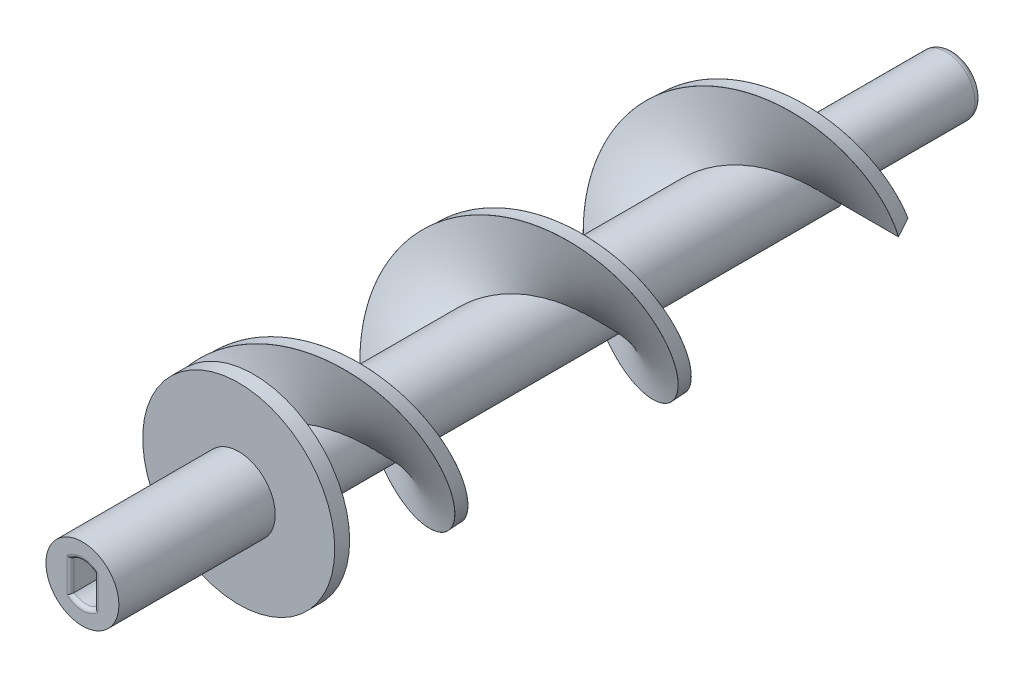
SolidWorks part; units mm, degrees
ref_plane "Front Plane" through (0, 0, 0) normal (0, 0, 1) x (1, 0, 0)
ref_plane "Top Plane" through (0, 0, 0) normal (0, 1, 0) x (1, 0, 0)
ref_plane "Right Plane" through (0, 0, 0) normal (1, 0, 0) x (0, 0, -1)
sketch "Sketch2" plane through (0, 0, 0) normal (0, 0, 1) x (1, 0, 0)
  circle A0 centre (0, 0) radius 4.9
  dimension "D1" = 9.8
extrude "Boss-Extrude1" add sketch "Sketch2" along normal mid plane 98
sketch "Sketch3" plane through (0, 0, -49) normal (0, 0, -1) x (-1, 0, 0)
  circle A0 centre (0, 0) radius 4
curve "Helix/Spiral1" pitch 30 height 75 radius 4 centre (0, 0, -49) axis (0, 0, 1) start towards (1, 0, 0)
ref_plane "Plane1" through (4, 0, -49) normal (0, 0.6422, 0.7666) x (1, 0, 0)
sketch "Sketch5" plane through (4, 0, -49) normal (0, 0.6422, 0.7666) x (1, 0, 0)
  line L1 (-0.1, 0) -> (8.89, 0)
  line L2 (-0.1, 0) -> (-0.1, -2)
  line L3 (-0.1, -2) -> (8.89, -2)
  line L4 (8.9, -0.01) -> (8.9, -1.99)
  arc A0 (8.89, -2) -> (8.9, -1.99) centre (8.89, -1.99) ccw
  arc A1 (8.89, 0) -> (8.9, -0.01) centre (8.89, -0.01) cw
  point P14 (8.9, 0)
  point P15 (0, 0)
  dimension "D3" = 0.01
  dimension "D4" = 1
  dimension "D1" = 9
  dimension "D2" = 2
sweep "Sweep1" add profiles "Sketch5" path "Helix/Spiral1"
sketch "Sketch6" plane through (0, 0, 49) normal (0, 0, 1) x (1, 0, 0)
  line L1 (-1.6, -2.0494) -> (1.6, -2.0494)
  line L2 (-1.6, -2.0494) -> (-1.6, 2.0494)
  line L3 (-1.6, 2.0494) -> (1.6, 2.0494)
  line L4 (1.6, -2.0494) -> (1.6, 2.0494)
  line L5 (-1.6, -2.0494) -> (1.6, 2.0494) construction
  line L6 (-1.6, 2.0494) -> (1.6, -2.0494) construction
  circle A0 centre (0, 0) radius 2.6
  dimension "D1" = 5.2
  dimension "D2" = 3.2
extrude "Cut-Extrude1" cut sketch "Sketch6" against normal blind 9 contours L3 A0 | L1 L4 L3 L2 | L1 A0 region at (0, 0, 49) region at (0, -2.2718, 49) region at (0, 2.2718, 49)
sketch "Sketch7" plane through (0, 0, -49) normal (0, 0, -1) x (-1, 0, 0)
  circle A0 centre (0, 0) radius 3.9
  dimension "D1" = 7.8
extrude "Boss-Extrude3" add sketch "Sketch7" along normal blind 19
fillet "Fillet1" radius 1 1 edges at (-3.9, 0, -68)
fillet "Fillet2" radius 0.5 4 edges at (0, -2.6, 49) (1.6, 0, 49) (0, 2.6, 49) (-1.6, 0, 49)
sketch "Sketch8" plane through (0, 0, 49) normal (0, 0, 1) x (1, 0, 0)
  circle A0 centre (0, 0) radius 12.9
  circle A1 centre (0, 0) radius 4.9
  dimension "D1" = 25.8
extrude "Boss-Extrude5" add sketch "Sketch8" against normal blind 2 from offset 21 offset against normal yes
